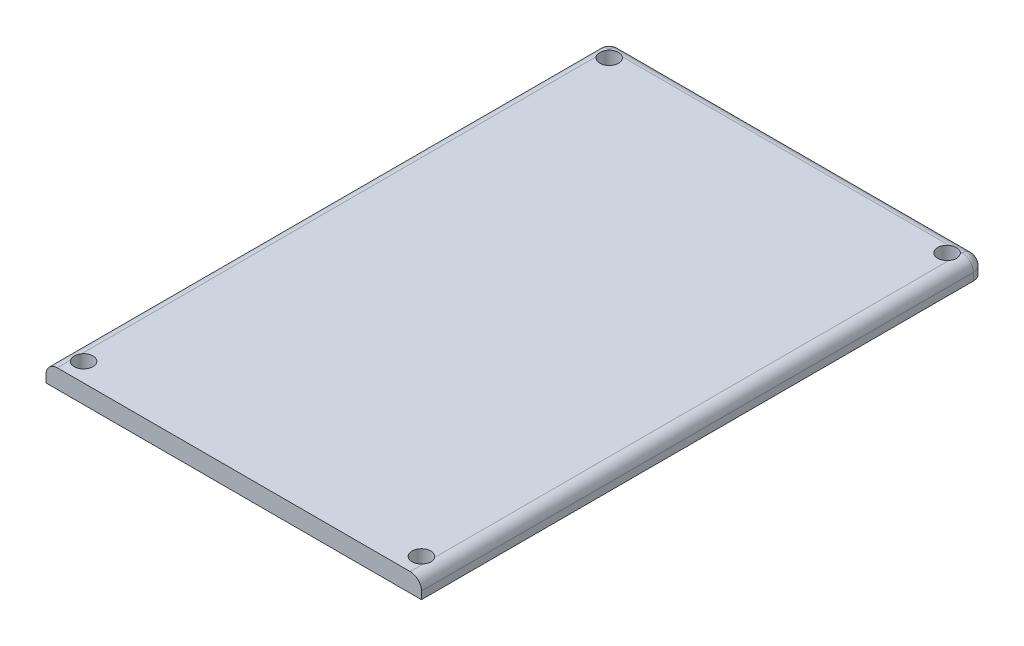
SolidWorks part; units mm, degrees
ref_plane "Front Plane" through (0, 0, 0) normal (0, 0, 1) x (1, 0, 0)
ref_plane "Top Plane" through (0, 0, 0) normal (0, 1, 0) x (1, 0, 0)
ref_plane "Right Plane" through (0, 0, 0) normal (1, 0, 0) x (0, 0, -1)
sketch "Sketch1" plane through (0, 0, 0) normal (0, 1, 0) x (1, 0, 0)
  line L0 (0, 0) -> (-116825.3215, 0) construction
  line L1 (0, 0) -> (0, -116825.3215) construction
  line L3 (-50, 75) -> (50, 75)
  line L4 (-50, 75) -> (-50, -75)
  line L5 (-50, -75) -> (50, -75)
  line L6 (50, 75) -> (50, -75)
  line L7 (-50, 75) -> (50, -75) construction
  line L8 (-50, -75) -> (50, 75) construction
  point P5 (0, 0)
  dimension "D1" = 150
  dimension "D2" = 100
extrude "Boss-Extrude1" add sketch "Sketch1" along normal blind 5
sketch "Sketch2" plane through (0, 5, 0) normal (0, 1, 0) x (1, 0, 0)
  line L0 (0, 0) -> (-50000, 0) construction
  line L1 (0, 0) -> (0, -50000) construction
  line L2 (40, -65) -> (40, 65) construction
  line L3 (40, 65) -> (-40, 65) construction
  line L4 (-40, 65) -> (-40, -65) construction
  line L5 (-40, -65) -> (40, -65) construction
  line L6 (50, -75) -> (50, 75)
  line L7 (50, 75) -> (-50, 75)
  line L8 (-50, 75) -> (-50, -75)
  line L9 (-50, -75) -> (50, -75)
  line L10 (50, -75) -> (50, 75) construction
  line L11 (50, 75) -> (-50, 75) construction
  line L12 (-50, 75) -> (-50, -75) construction
  line L13 (-50, -75) -> (50, -75) construction
  line L14 (-40, 65) -> (-50, 75) construction
  circle A0 centre (-45, 70) radius 2.5
  circle A1 centre (45, 70) radius 2.5
  circle A2 centre (45, -70) radius 2.5
  circle A3 centre (-45, -70) radius 2.5
  dimension "D3" = 5
  dimension "D1" = 0
  dimension "D2" = 10
extrude "Cut-Extrude1" cut sketch "Sketch2" against normal through all
fillet "Fillet1" radius 3 5 edges at (-50, 2.5, -75) (50, 2.5, -75) (0, 5, -75) (50, 5, 0) (-50, 5, 0)
